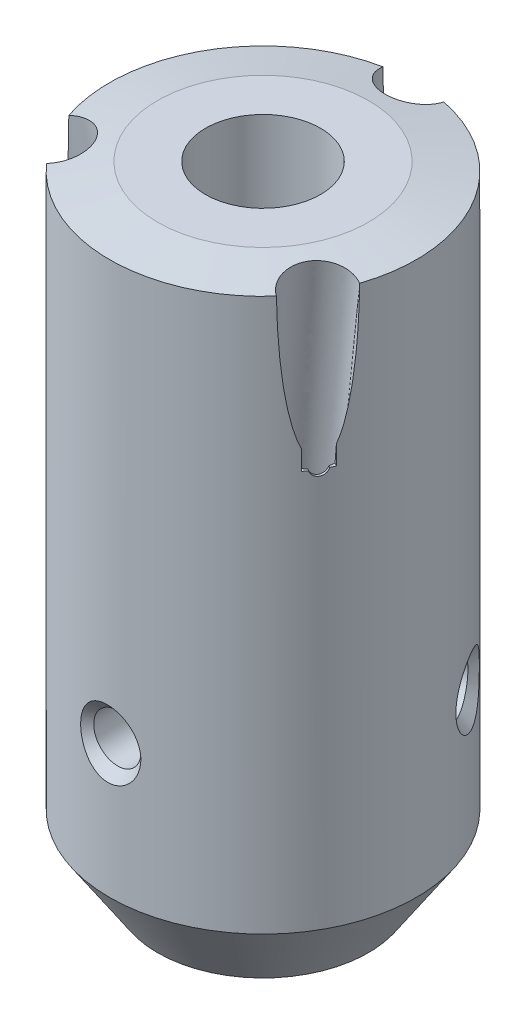
SolidWorks part; units mm, degrees
ref_plane "Front Plane" through (0, 0, 0) normal (0, 0, 1) x (1, 0, 0)
ref_plane "Top Plane" through (0, 0, 0) normal (0, 1, 0) x (1, 0, 0)
ref_plane "Right Plane" through (0, 0, 0) normal (1, 0, 0) x (0, 0, -1)
sketch "Sketch1" plane through (0, 0, 0) normal (0, 1, 0) x (1, 0, 0)
  circle A0 centre (0, 0) radius 16
  dimension "D1" = 32
extrude "Boss-Extrude1" add sketch "Sketch1" along normal blind 66
sketch "Sketch2" plane through (0, 66, 0) normal (0, 1, 0) x (1, 0, 0)
  circle A0 centre (0, 0) radius 6
  dimension "D1" = 12
extrude "Cut-Extrude1" cut sketch "Sketch2" against normal blind 15
sketch "Sketch3" plane through (0, 0, 0) normal (0, -1, 0) x (1, 0, 0)
  circle A0 centre (0, 0) radius 6
  dimension "D1" = 12
extrude "Cut-Extrude2" cut sketch "Sketch3" against normal blind 30
sketch "Sketch4" plane through (0, 0, 0) normal (0, 0, 1) x (1, 0, 0)
  line L0 (-11, 66) -> (-16, 65.1184)
  line L1 (16, 66) -> (-16, 66) construction
  line L2 (-16, 65.1184) -> (-16, 66)
  line L3 (-16, 66) -> (-11, 66)
  line L4 (0, 66) -> (0, 0) construction
  dimension "D1" = 10
  dimension "D2" = 11
revolve "Cut-Revolve1" cut sketch "Sketch4" angle 360 about L4
sketch "Sketch5" plane through (0, 0, 0) normal (0, 0, 1) x (1, 0, 0)
  line L0 (-16, 7.5) -> (-11, 0)
  line L1 (-16, 65.1184) -> (-16, 0) construction
  line L2 (-16, 0) -> (16, 0) construction
  line L3 (-11, 0) -> (-16, 0)
  line L4 (-16, 0) -> (-16, 7.5)
  dimension "D1" = 11
  dimension "D2" = 58.5
revolve "Cut-Revolve2" cut sketch "Sketch5" angle 360 about axis through (0, 66, 0) along (0, -1, 0) reverse direction yes
hole_wizard "CSK for M5 Countersunk Flat Head Screw1" positions "3DSketch1" profile "Sketch8" countersink size "M5" standard "ISO"
sketch3d "3DSketch1"
  point P0 (-0.2057, 21.2967, 15.9987)
sketch "Sketch8" plane through (-0.2057, 21.2967, 15.9987) normal (0, 1, 0) x (0.9999, 0, 0.0129)
  line L0 (0, 0) -> (0, 8)
  line L1 (0, 8) -> (2.5, 8)
  line L2 (2.5, 8) -> (2.5, 1)
  line L3 (2.5, 1) -> (3.5, 0)
  line L5 (3.5, 0) -> (0, 0)
  line L6 (-2.5, 1) -> (-3.5, 0) construction
  line L10 (0, 8) -> (-2.5, 8) construction
  line L11 (0, -6.35) -> (0, 107.95) construction
  dimension "Hole Dia." = 5
  dimension "Hole Depth" = 8
  dimension "Near C'Sink Dia." = 7
  dimension "Near C'Sink Angle" = 90
  dimension "Drill Angle" = 180
pattern_circular "CirPattern1" count 3 over 360 about axis through (0, 66, 0) along (0, -1, 0) of "CSK for M5 Countersunk Flat Head Screw1"
sketch "Sketch12" plane through (0, 66, 0) normal (0, 1, 0) x (1, 0, 0)
  circle A0 centre (0, 16) radius 3.2
  circle A1 centre (0, 0) radius 16 construction
  dimension "D1" = 6.4
sketch "Sketch15" plane through (0, 0, 0) normal (0, 1, 0) x (1, 0, 0)
  line L0 (0, 4.2133) -> (0, 0) construction
  circle A0 centre (0, 4.2133) radius 2.67
  dimension "D1" = 5.34
  dimension "D2" = 4.2133
loft "Cut-Loft5" cut section "Sketch15" section "Sketch12" connector at (-2.4929, 0, -3.257) connector at (-2.863, 66, -17.4294)
ref_plane "Plane2" through (0, 0, -16) normal (0, 0, 1) x (1, 0, 0)
sketch "Sketch16" plane through (0, 0, -16) normal (0, 0, 1) x (1, 0, 0)
  line L0 (0, 65.1184) -> (0, 0) construction
  line L1 (1.335, 49.1184) -> (0.8094, 49.1184)
  line L2 (-11, 0) -> (11, 0) construction
  line L3 (-0.8094, 49.1184) -> (-1.335, 49.1184)
  line L4 (1.335, 49.1184) -> (1.335, 51.9824)
  line L5 (1.335, 51.9824) -> (-1.335, 51.9824)
  line L6 (-1.335, 51.9824) -> (-1.335, 49.1184)
  arc A0 (-0.8094, 49.1184) -> (0.8094, 49.1184) centre (0, 49.3235) ccw
  dimension "D5" = 1.67
  dimension "D1" = 16
  dimension "D2" = 2.67
  dimension "D3" = 1.335
  dimension "D4" = 49.1184
  dimension "D6" = 0.2051
  dimension "D7" = 2.8641
extrude "Cut-Extrude3" cut sketch "Sketch16" along normal blind 4 contours A0 L1 L4 L5 L6 L3
pattern_circular "CirPattern2" count 3 over 360 about axis through (0, 51, 0) along (0, 1, 0) of "Cut-Extrude3", "Cut-Loft5"
